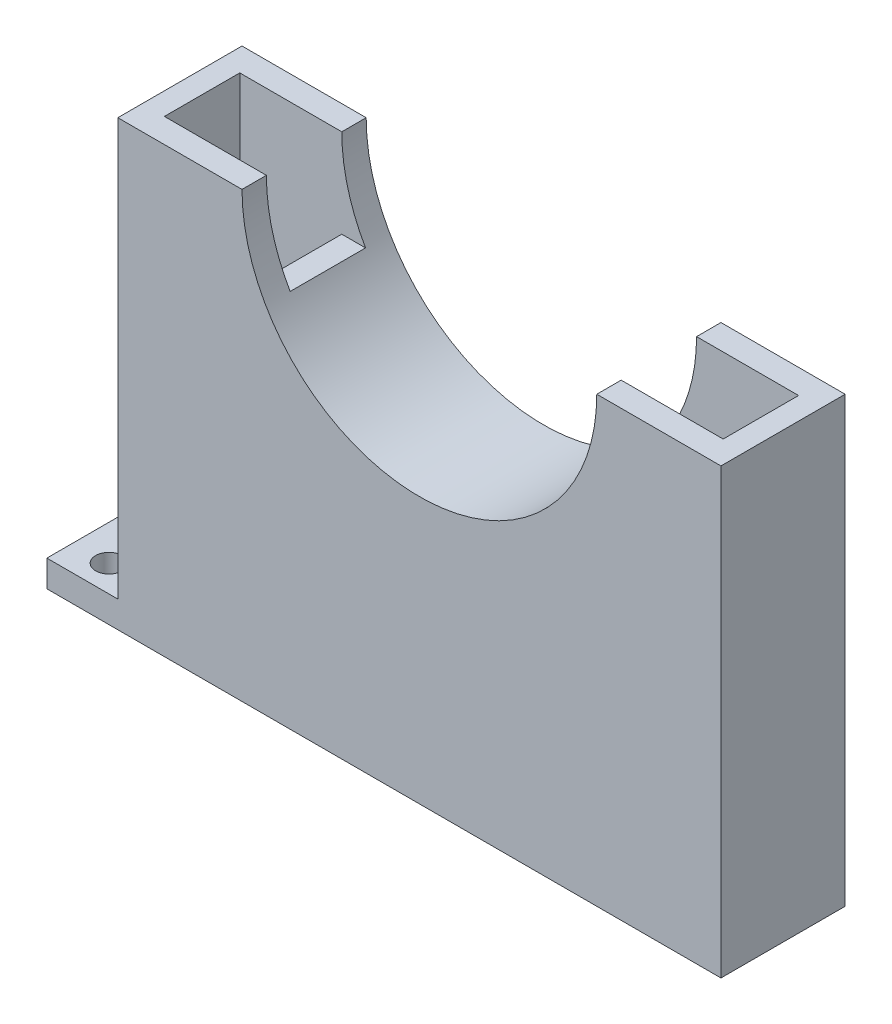
SolidWorks part; units mm, degrees
ref_plane "Front Plane" through (0, 0, 0) normal (0, 0, 1) x (1, 0, 0)
ref_plane "Top Plane" through (0, 0, 0) normal (0, 1, 0) x (1, 0, 0)
ref_plane "Right Plane" through (0, 0, 0) normal (1, 0, 0) x (0, 0, -1)
sketch "Sketch1" plane through (0, 0, 0) normal (0, 0, 1) x (1, 0, 0)
  line L0 (0, 0) -> (0, 3)
  line L1 (0, 3) -> (8, 3)
  line L2 (0, 0) -> (76, 0)
  line L3 (76, 0) -> (76, 50)
  line L4 (8, 3) -> (8, 50)
  line L5 (8, 50) -> (22, 50)
  line L6 (76, 50) -> (62, 50)
  arc A1 (62, 50) -> (22, 50) centre (42, 50) cw
  dimension "D1" = 14
  dimension "D2" = 20
  dimension "D3" = 3
  dimension "D4" = 50
  dimension "D5" = 8
extrude "Boss-Extrude1" add sketch "Sketch1" along normal blind 14
sketch "Sketch2" plane through (0, 0, 0) normal (0, -1, 0) x (1, 0, 0)
  line L0 (42, 14) -> (42, 0) construction
  line L1 (0, 14) -> (76, 14) construction
  line L2 (0, 0) -> (76, 0) construction
  line L3 (62, 14) -> (22, 14) construction
  line L4 (73.5, 11.25) -> (62, 11.25)
  line L5 (62, 11.25) -> (62, 2.75)
  line L6 (62, 2.75) -> (73.5, 2.75)
  line L7 (73.5, 2.75) -> (73.5, 11.25)
  line L10 (76, 14) -> (76, 0) construction
  line L11 (22, 2.75) -> (10.5, 2.75)
  line L12 (22, 11.25) -> (22, 2.75)
  line L13 (10.5, 11.25) -> (22, 11.25)
  line L14 (10.5, 2.75) -> (10.5, 11.25)
  point P14 (76, 7)
  point P15 (73.5, 7)
  dimension "D1" = 11.5
  dimension "D2" = 8.5
  dimension "D3" = 2.5
extrude "Cut-Extrude1" cut sketch "Sketch2" against normal up to surface (50 mm away) up to face at (15, 50, 7)
sketch "Sketch3" plane through (0, 3, 0) normal (0, 1, 0) x (1, 0, 0)
  line L0 (4, -3) -> (4, -11) construction
  line L1 (0, -14) -> (0, 0) construction
  line L4 (8, -14) -> (0, -14) construction
  circle A0 centre (4, -3) radius 1.5
  circle A1 centre (4, -11) radius 1.5
  point P7 (4, -14)
  point P10 (0, -7)
  point P11 (4, -7)
  dimension "D1" = 3
  dimension "D2" = 3
  dimension "D3" = 8
extrude "screw holes" cut sketch "Sketch3" against normal up to surface (3 mm away) up to face at (67.75, 0, 7)
sketch "Sketch4" plane through (0, 50, 0) normal (0, 1, 0) x (1, 0, 0)
  line L0 (8, -14) -> (76, -14) construction
  line L1 (10.5, -11.25) -> (73.5, -11.25)
  line L5 (73.5, -2.75) -> (73.5, -11.25)
  line L9 (10.5, -2.75) -> (10.5, -11.25)
  line L10 (10.5, -2.75) -> (73.5, -2.75)
  line L11 (10.5, -2.75) -> (10.5, -11.25) construction
  point P4 (10.5, -2.75)
extrude "Cut-Extrude2" cut sketch "Sketch4" against normal blind 10
